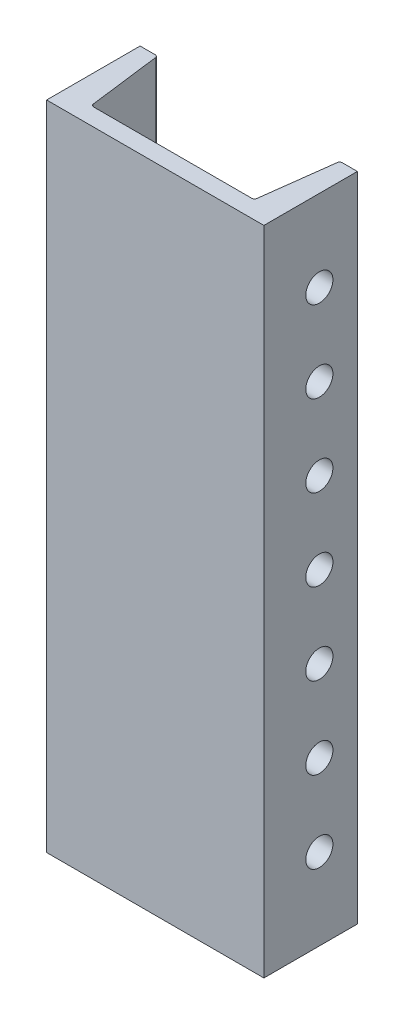
SolidWorks part; units mm, degrees
material "ASTM A36 Steel"
ref_plane "Front Plane" through (0, 0, 0) normal (0, 0, 1) x (1, 0, 0)
ref_plane "Top Plane" through (0, 0, 0) normal (0, 1, 0) x (1, 0, 0)
ref_plane "Right Plane" through (0, 0, 0) normal (1, 0, 0) x (0, 0, -1)
sketch "Sketch1" plane through (0, 0, 0) normal (0, 1, 0) x (1, 0, 0)
  line L0 (0, 0) -> (101.6, 0) construction
  line L1 (0, 0) -> (0, 8.1534) construction
  line L2 (101.6, 0) -> (101.6, 8.1534) construction
  line L3 (0, 8.1534) -> (101.6, 8.1534) construction
  line L4 (0, 0) -> (0, 43.7134) construction
  line L5 (0, 43.7134) -> (8.1534, 43.7134) construction
  line L6 (8.1534, 43.7134) -> (12.7, 8.1534) construction
  line L7 (12.7, 8.1534) -> (88.9, 8.1534) construction
  line L8 (88.9, 8.1534) -> (93.4466, 43.7134) construction
  line L9 (93.4466, 43.7134) -> (101.6, 43.7134) construction
  line L10 (101.6, 43.7134) -> (101.6, 8.1534) construction
  line L11 (0, 0) -> (101.6, 0)
  line L12 (101.6, 0) -> (101.6, 43.7134)
  line L13 (101.6, 43.7134) -> (93.4466, 43.7134)
  line L14 (93.4466, 43.7134) -> (88.9, 8.1534)
  line L15 (88.9, 8.1534) -> (12.7, 8.1534)
  line L16 (12.7, 8.1534) -> (8.1534, 43.7134)
  line L17 (8.1534, 43.7134) -> (0, 43.7134)
  line L18 (0, 43.7134) -> (0, 0)
  dimension "D1" = 101.6
  dimension "D2" = 8.1534
  dimension "D3" = 43.7134
  dimension "D4" = 8.1534
  dimension "D5" = 12.7
  dimension "D6" = 12.7
extrude "Boss-Extrude1" add sketch "Sketch1" along normal blind 304.8 contours L15 L16 L17 L18 L11 L12 L13 L14
ref_plane "Plane1" through (0, 152.4, 0) normal (0, 1, 0) x (1, 0, 0)
sketch "Sketch2" plane through (101.6, 0, 0) normal (1, 0, 0) x (0, 0, -1)
  line L0 (25.9334, 304.8) -> (25.9334, 0) construction
  line L3 (25.9334, 152.4) -> (0, 152.4) construction
  line L4 (0, 304.8) -> (0, 0) construction
  line L5 (0, 152.4) -> (43.7134, 152.4) construction
  line L6 (43.7134, 304.8) -> (43.7134, 0) construction
  line L8 (0, 304.8) -> (43.7134, 304.8) construction
  circle A0 centre (25.9334, 266.7) radius 6.35
  circle A1 centre (25.9334, 152.4) radius 6.35
  circle A2 centre (25.9334, 190.5) radius 6.35
  circle A3 centre (25.9334, 228.6) radius 6.35
  circle A4 centre (25.9334, 114.3) radius 6.35
  circle A5 centre (25.9334, 76.2) radius 6.35
  circle A6 centre (25.9334, 38.1) radius 6.35
  dimension "D1" = 38.1
  dimension "D2" = 152.4
  dimension "D5" = 12.7
  dimension "D6" = 12.7
  dimension "D7" = 12.7
  dimension "D8" = 12.7
  dimension "D3" = 76.2
  dimension "D4" = 114.3
  dimension "D9" = 17.78
  dimension "D10" = 17.78
extrude "Cut-Extrude1" cut sketch "Sketch2" against normal blind 304.8
fillet "Fillet1" radius 1.27 4 edges at (88.9, 152.4, -8.1534) (8.1534, 152.4, -43.7134) (93.4466, 152.4, -43.7134) (12.7, 152.4, -8.1534)
